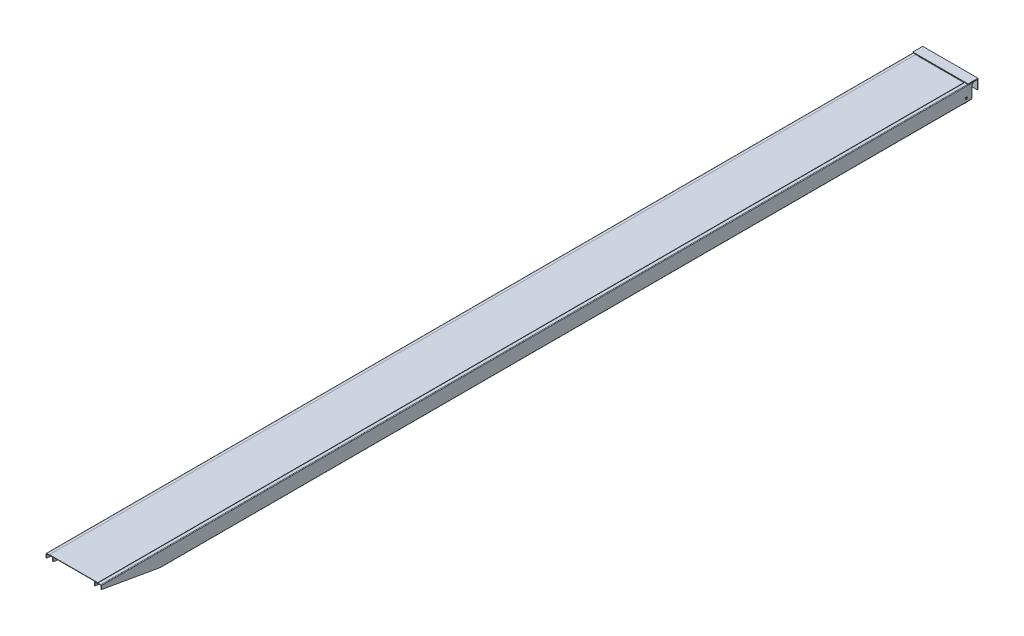
SolidWorks part; units mm, degrees
note: The reader was unsure of these and kept them because the rebuilt part matched: shared geometry of "Sketch16<3>", "Sketch16<4>".
material "Plain Carbon Steel"
ref_plane "Front Plane" through (0, 0, 0) normal (0, 0, 1) x (1, 0, 0)
ref_plane "Top Plane" through (0, 0, 0) normal (0, 1, 0) x (1, 0, 0)
ref_plane "Right Plane" through (0, 0, 0) normal (1, 0, 0) x (0, 0, -1)
sketch "Sketch1" plane through (0, 0, 0) normal (0, 1, 0) x (1, 0, 0)
  line L1 (-120, -2175) -> (120, -2175)
  line L2 (-120, -2175) -> (-120, 2175)
  line L3 (-120, 2175) -> (120, 2175)
  line L4 (120, -2175) -> (120, 2175)
  line L5 (-120, -2175) -> (120, 2175) construction
  line L6 (-120, 2175) -> (120, -2175) construction
  point P0 (0, 0)
  dimension "D1" = 4350
  dimension "D2" = 240
extrude "Boss-Extrude1" add sketch "Sketch1" against normal blind 2
sketch "Sketch2" plane through (0, -2, 0) normal (0, -1, 0) x (1, 0, 0)
  line L0 (0, -2292.7152) -> (0, 2292.7152) construction
  line L1 (-120, -2175) -> (-120, 2175)
  line L2 (120, -2175) -> (-120, -2175) construction
  line L3 (-120, 2175) -> (120, 2175) construction
  line L5 (120, -2175) -> (120, 2175)
  line L6 (-120, -2175) -> (-120, 2175) construction
other "Structural Member1"
ref_plane "Plane1" through (-120, -38.55, -2175) normal (0, 0, 1) x (-1, 0, 0)
sketch "Sketch111" plane through (-120, -38.55, -2175) normal (0, 0, 1) x (-1, 0, 0)
  line L0 (-14.25, 34.35) -> (14.25, 34.35)
  line L1 (-14.25, 36.55) -> (14.25, 36.55)
  line L2 (-17.25, 33.55) -> (-17.25, -33.55)
  line L3 (-14.25, -36.55) -> (14.25, -36.55)
  line L4 (17.25, 33.55) -> (17.25, -33.55)
  line L5 (-17.25, 36.55) -> (17.25, -36.55) construction
  line L6 (-17.25, -36.55) -> (17.25, 36.55) construction
  line L7 (15.05, 33.55) -> (15.05, -33.55)
  line L8 (-14.25, -34.35) -> (14.25, -34.35)
  line L9 (-15.05, 33.55) -> (-15.05, -33.55)
  arc A0 (14.25, -36.55) -> (17.25, -33.55) centre (14.25, -33.55) ccw
  arc A1 (-17.25, -33.55) -> (-14.25, -36.55) centre (-14.25, -33.55) ccw
  arc A2 (14.25, 36.55) -> (17.25, 33.55) centre (14.25, 33.55) cw
  arc A3 (-14.25, 36.55) -> (-17.25, 33.55) centre (-14.25, 33.55) ccw
  arc A4 (14.25, 34.35) -> (15.05, 33.55) centre (14.25, 33.55) cw
  arc A5 (14.25, -34.35) -> (15.05, -33.55) centre (14.25, -33.55) ccw
  arc A6 (-15.05, -33.55) -> (-14.25, -34.35) centre (-14.25, -33.55) ccw
  arc A7 (-14.25, 34.35) -> (-15.05, 33.55) centre (-14.25, 33.55) ccw
  point P0 (0, 0)
  point P30 (0, 36.55)
  point P31 (-17.25, 0)
  point P32 (0, -36.55)
  point P33 (17.25, 0)
  point P34 (0, 0)
  dimension "D3" = 3
  dimension "D1" = 73.1
  dimension "D2" = 34.5
  dimension "D4" = 2.2
sketch "Sketch12" plane through (0, 0, 0) normal (1, 0, 0) x (0, 0, -1)
  line L0 (2148, -17.5) -> (2148, -66.3362)
  line L1 (2161.5, -4) -> (2316.1356, -4)
  line L3 (2148, -175.5442) -> (2316.1356, -175.5442)
  line L4 (2316.1356, -175.5442) -> (2316.1356, -4)
  line L5 (2138, -76.3362) -> (2114.9704, -76.3362)
  line L6 (0, -2) -> (0, -302.245) construction
  line L7 (2175, -2) -> (-2175, -2) construction
  line L8 (-2316.1356, -4) -> (-2274.9185, -4.5452)
  line L9 (-2316.1356, -175.5442) -> (-2316.1356, -4)
  line L10 (-1874.9185, -175.5442) -> (-2316.1356, -175.5442)
  line L11 (-1874.9185, -74.3952) -> (-1874.9185, -175.5442)
  line L12 (-2274.9185, -4.5452) -> (-1874.9185, -74.3952)
  line L13 (2175, -5) -> (2175, -72.1) construction
  line L15 (2114.9704, -76.3362) -> (2114.9704, -175.5442)
  line L16 (2114.9704, -175.5442) -> (2148, -175.5442)
  arc A0 (2161.5, -4) -> (2148, -17.5) centre (2161.5, -17.5) ccw
  arc A1 (2138, -76.3362) -> (2148, -66.3362) centre (2138, -66.3362) ccw
  dimension "D2" = 27
  dimension "D3" = 10
  dimension "D1" = 2
extrude "Cut-ExtrudeMainRailProfile" cut sketch "Sketch12" against normal through all and the other way through all
sketch "Sketch17" plane through (0, -2, 0) normal (0, -1, 0) x (1, 0, 0)
  line L0 (-102.75, 1824.9185) -> (102.75, 1824.9185)
  line L1 (-102.75, -2075) -> (102.75, -2075)
  line L2 (-102.75, 524.9457) -> (102.75, 524.9457)
  line L4 (-102.75, -775.0272) -> (102.75, -775.0272)
  line L5 (0, 1824.9185) -> (0, 524.9457) construction
  line L6 (0, 524.9457) -> (0, -775.0272) construction
  line L7 (0, -775.0272) -> (0, -2075) construction
  line L8 (0, -2292.7152) -> (0, 2292.7152) construction
  line L9 (120, -2175) -> (-120, -2175) construction
  line L11 (-136.1819, 1874.9185) -> (-103.8181, 1874.9185) construction
  line L12 (-102.75, 1888.0618) -> (-102.75, -2146.1718) construction
  dimension "D1" = 100
  dimension "D2" = 50
other "Structural Member2"
ref_plane "Plane2" through (-102.75, -19.8, 1824.9185) normal (1, 0, 0) x (0, 0, 1)
sketch "Sketch19" plane through (-102.75, -19.8, 1824.9185) normal (1, 0, 0) x (0, 0, 1)
  line L1 (-14.8, -17.8) -> (14.8, -17.8)
  line L2 (-17.8, -14.8) -> (-17.8, 14.8)
  line L3 (-14.8, 17.8) -> (14.8, 17.8)
  line L4 (17.8, -14.8) -> (17.8, 14.8)
  line L5 (-17.8, -17.8) -> (17.8, 17.8) construction
  line L6 (-17.8, 17.8) -> (17.8, -17.8) construction
  line L7 (-14.8, 16.6) -> (14.8, 16.6)
  line L8 (-16.6, 14.8) -> (-16.6, -14.8)
  line L9 (-14.8, -16.6) -> (14.8, -16.6)
  line L10 (16.6, 14.8) -> (16.6, -14.8)
  line L11 (-16.6, 16.6) -> (16.6, -16.6) construction
  line L12 (-16.6, -16.6) -> (16.6, 16.6) construction
  arc A0 (14.8, 17.8) -> (17.8, 14.8) centre (14.8, 14.8) cw
  arc A1 (14.8, -17.8) -> (17.8, -14.8) centre (14.8, -14.8) ccw
  arc A2 (-14.8, -17.8) -> (-17.8, -14.8) centre (-14.8, -14.8) cw
  arc A3 (-17.8, 14.8) -> (-14.8, 17.8) centre (-14.8, 14.8) cw
  arc A4 (-16.6, -14.8) -> (-14.8, -16.6) centre (-14.8, -14.8) ccw
  arc A5 (14.8, -16.6) -> (16.6, -14.8) centre (14.8, -14.8) ccw
  arc A6 (14.8, 16.6) -> (16.6, 14.8) centre (14.8, 14.8) cw
  arc A7 (-14.8, 16.6) -> (-16.6, 14.8) centre (-14.8, 14.8) ccw
  point P0 (0, 0)
  point P5 (0, 0)
  point P35 (0, -17.8)
  point P36 (-17.8, 0)
  point P37 (17.8, 0)
  point P38 (0, 17.8)
  point P39 (0, 0)
  dimension "D4" = 3
  dimension "D5" = 1.8
  dimension "D1" = 35.6
  dimension "D2" = 35.6
  dimension "D3" = 1.2
sketch "Sketch13" plane through (0, 0, 0) normal (0, 1, 0) x (1, 0, 0)
  line L1 (-134.25, 2175) -> (134.25, 2175)
  line L2 (-134.25, 2175) -> (-134.25, 2125)
  line L3 (-134.25, 2125) -> (134.25, 2125)
  line L4 (134.25, 2175) -> (134.25, 2125)
  line L5 (-134.25, -2175) -> (-134.25, 2175) construction
  dimension "D1" = 50
extrude "Cut-ExtrudeTreadClearance" cut sketch "Sketch13" against normal up to surface (2 mm away) up to face at (-120, -2, 0)
sketch "Sketch14" plane through (0, 0, 0) normal (1, 0, 0) x (0, 0, -1)
  line L0 (2129, 1) -> (2178, 1)
  line L3 (2178, 1) -> (2178, -48)
  line L4 (2178, -48) -> (2175, -48)
  line L5 (2175, -48) -> (2175, -2)
  line L6 (2292.7152, -2) -> (-2292.7152, -2) construction
  line L7 (2175, -2) -> (2129, -2)
  line L8 (2129, -2) -> (2129, 1)
  line L10 (2175, -4) -> (2175, -2) construction
  dimension "D1" = 49
  dimension "D2" = 3
  dimension "D3" = 3
  dimension "D4" = 49
extrude "Boss-ExtrudeAngleIron" add sketch "Sketch14" against normal up to surface and the other way up to surface separate body
sketch "Sketch15" plane through (0, -75.1, 0) normal (0, -1, 0) x (1, 0, 0)
  line L1 (-135.05, -2196.3116) -> (-104.95, -2196.3116)
  line L2 (-135.05, -2196.3116) -> (-135.05, -2073)
  line L3 (-135.05, -2073) -> (-104.95, -2073)
  line L4 (-104.95, -2196.3116) -> (-104.95, -2073)
  line L6 (0, -2075) -> (0, -2221.887) construction
  line L7 (0, -2292.7152) -> (0, 2292.7152) construction
  line L8 (104.95, -2196.3116) -> (104.95, -2073)
  line L9 (135.05, -2073) -> (104.95, -2073)
  line L14 (-135.05, 1888.0618) -> (-135.05, -2146.1718) construction
  line L15 (-104.95, 1888.0618) -> (-104.95, -2146.1718) construction
  line L16 (135.05, -2196.3116) -> (135.05, -2073)
  line L17 (135.05, -2196.3116) -> (104.95, -2196.3116)
extrude "Cut-ExtrudeWheelHoles" cut sketch "Sketch15" against normal up to next
sketch "Sketch16" plane through (0, 0, 0) normal (1, 0, 0) x (0, 0, -1)
  line L0 (2120, -81.1) -> (2027.8198, -81.1) construction
  line L2 (2145, -56.1) -> (2145, -111.0446) construction
  line L3 (2148, -17.5) -> (2148, -66.3362) construction
  line L4 (-1874.9185, -75.1) -> (2073, -75.1) construction
  circle A0 centre (2120, -56.1) radius 25
  circle A1 centre (2120, -56.1) radius 5
  dimension "D2" = 50
  dimension "D4" = 10
  dimension "D1" = 6
  dimension "D3" = 3
extrude "Cut-ExtrudeAxleHoles" cut sketch "Sketch16" against normal through all and the other way through all contours A1
extrude "Boss-ExtrudeLeftWheel" add sketch "Sketch16<3>" against normal blind 22 from offset 109 separate body offset against normal yes
sketch "Sketch16<3>" plane through (0, 0, 0) normal (1, 0, 0) x (0, 0, -1) same geometry as "Sketch16"
extrude "Boss-ExtrudeRightWheel" add sketch "Sketch16<4>" along normal blind 22 from offset 109 separate body
sketch "Sketch16<4>" plane through (0, 0, 0) normal (1, 0, 0) x (0, 0, -1) same geometry as "Sketch16"
